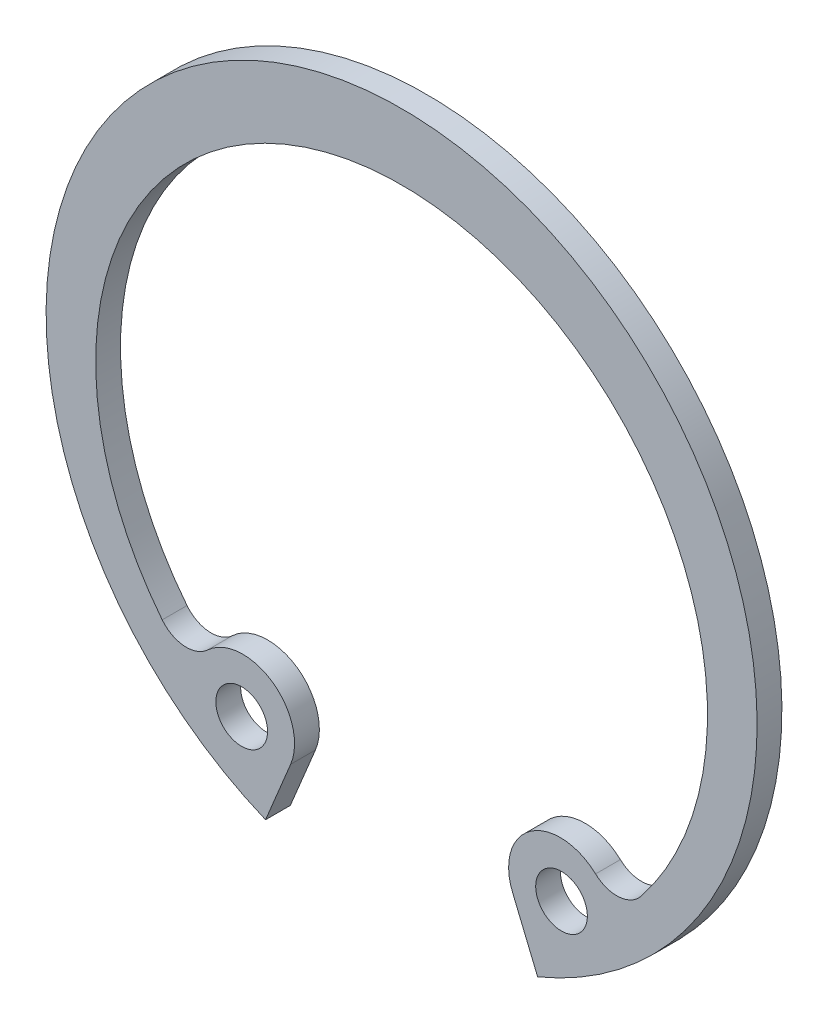
SolidWorks part; units mm, degrees
material "65Mn"
ref_plane "前视" through (0, 0, 0) normal (0, 0, 1) x (1, 0, 0)
ref_plane "上视" through (0, 0, 0) normal (0, 1, 0) x (1, 0, 0)
ref_plane "右视" through (0, 0, 0) normal (1, 0, 0) x (0, 0, -1)
sketch "尺寸草图" plane through (0, 0, 0) normal (0, 0, 1) x (1, 0, 0)
  line L0 (-17.2, 0) -> (17.2, 0) construction
  line L1 (0, 0) -> (-14.8956, -8.6) construction
  circle A0 centre (0, 0) radius 17.2
  point P5 (-12.4, 0)
  point P6 (12.9, 0)
  point P7 (2.5, 0)
  point P8 (14.4, 0)
  point P10 (-2.95, 0)
  point P11 (-0.8, 0)
  point P12 (-5.45, 0)
  point P13 (-13.6, 0)
  point P14 (24.0755, 13.9)
  dimension "DD" = 34.4
  dimension "d" = 29.6
  dimension "RR" = 14.4
  dimension "R1" = 2.5
  dimension "R2" = 1.5
  dimension "a" = 5.45
  dimension "d1" = 2.5
  dimension "c" = 0.8
  dimension "s" = 1.2
  dimension "aa" = 45
sketch "草图1" plane through (0, 0, 0) normal (0, 0, 1) x (1, 0, 0)
  line L0 (0, 17.2) -> (0, -15.8907) construction
  line L1 (-5.3687, -12.9611) -> (-6.5822, -15.8907)
  line L2 (-7.795, -12.2859) -> (-7.6784, -12.0044) construction
  line L3 (0, 0) -> (-6.5822, -15.8907) construction
  line L4 (5.3687, -12.9611) -> (6.5822, -15.8907)
  arc A0 (6.5822, -15.8907) -> (-6.5822, -15.8907) centre (0, 0) ccw
  arc A1 (11.5817, -10.0143) -> (-11.5817, -10.0143) centre (0, -0.8) ccw
  circle A2 centre (-7.7367, -12.1451) radius 1.25
  arc A3 (-5.3687, -12.9611) -> (-9.3843, -10.1769) centre (-7.6784, -12.0044) ccw
  arc A4 (-9.3843, -10.1769) -> (-11.5817, -10.0143) centre (-10.4079, -9.0804) cw
  circle A5 centre (7.7367, -12.1451) radius 1.25
  arc A6 (5.3687, -12.9611) -> (9.3843, -10.1769) centre (7.6784, -12.0044) cw
  arc A7 (9.3843, -10.1769) -> (11.5817, -10.0143) centre (10.4079, -9.0804) ccw
  dimension "D1" = 34.4
  dimension "D2" = 29.6
  dimension "D5" = 2.5
  dimension "D7" = 2.5
  dimension "D8" = 1.5
  dimension "D3" = 0.8
  dimension "D6" = 14.4
  dimension "D9" = 5.45
  dimension "D4" = 22.5
extrude "基体-拉伸" add sketch "草图1" along normal blind 0.6 and the other way blind 0.6
equation "\"D1@草图1\" = \"DD@尺寸草图\" "
equation "\"D2@草图1\"=\"d@尺寸草图\""
equation "\"D3@草图1\" = \"c@尺寸草图\""
equation "\"D6@草图1\" = \"RR@尺寸草图\""
equation "\"D8@草图1\" = \"R2@尺寸草图\""
equation "\"D7@草图1\" = \"R1@尺寸草图\""
equation "\"D4@草图1\" = \"aa@尺寸草图\"/2"
equation "\"D9@草图1\" = \"a@尺寸草图\""
equation "\"D5@草图1\" = \"d1@尺寸草图\""
equation "\"D1@基体-拉伸\" = \"s@尺寸草图\"/2"
equation "\"D2@基体-拉伸\" = \"D1@基体-拉伸\""
